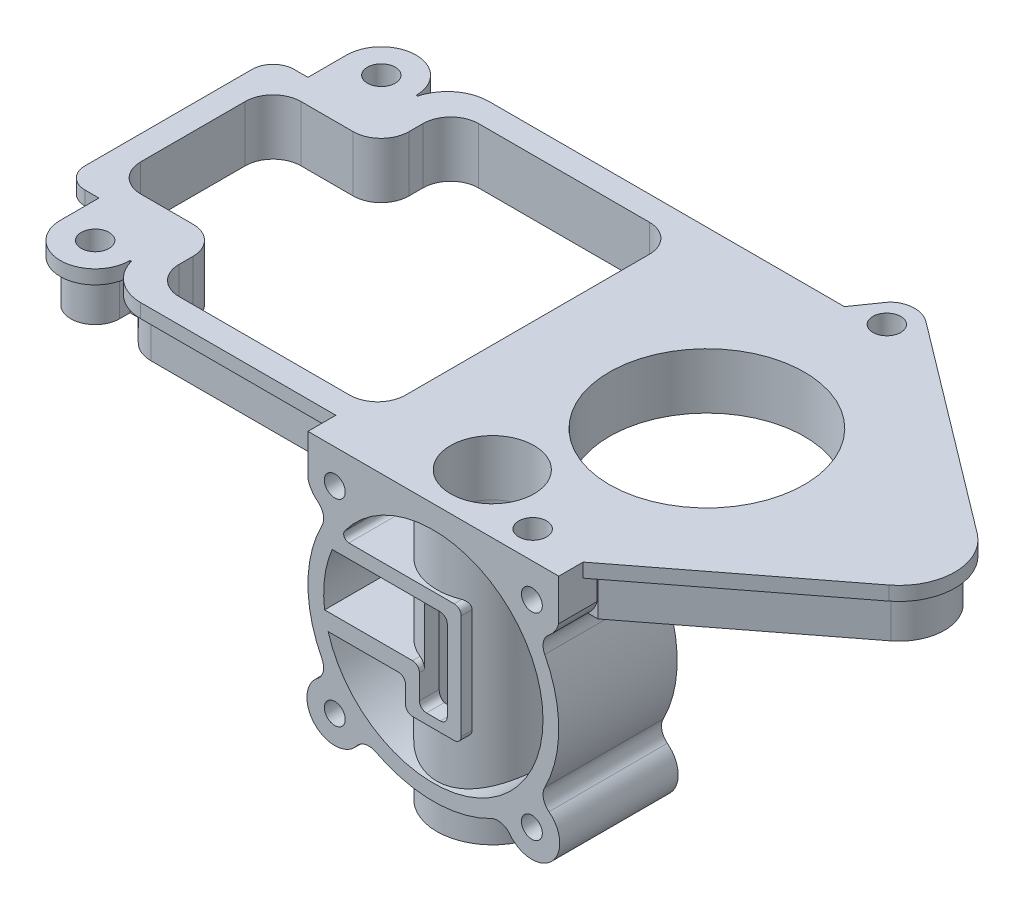
SolidWorks part; units mm, degrees
ref_plane "Płaszczyzna przednia" through (0, 0, 0) normal (0, 0, 1) x (1, 0, 0)
ref_plane "Płaszczyzna górna" through (0, 0, 0) normal (0, 1, 0) x (1, 0, 0)
ref_plane "Płaszczyzna prawa" through (0, 0, 0) normal (1, 0, 0) x (0, 0, -1)
sketch "Szkic1" plane through (0, 0, 0) normal (0, 0, 1) x (1, 0, 0)
  line L2 (-15.6121, -2) -> (-3, -2)
  line L5 (18, 19) -> (-18, 19)
  line L6 (18, 19) -> (18, 13.0853)
  line L7 (-18, 19) -> (-18, 13.0853)
  line L8 (-14.5245, 6.0642) -> (1, 6.0642)
  line L9 (4, 7.0642) -> (4, -7.9358)
  line L10 (-1, -7.5) -> (1, -7.5)
  line L12 (-15.1017, -4.4358) -> (-5, -4.4358)
  line L13 (-12.1244, 8.0642) -> (3, 8.0642)
  line L14 (-3, -8.9358) -> (3, -8.9358)
  line L15 (-2, -6.5) -> (-2, -3)
  line L16 (-4, -7.9358) -> (-4, -5.4358)
  line L17 (2, 5.0642) -> (2, -6.5)
  arc A0 (-15.1017, -4.4358) -> (-12.731, 9.2552) centre (0, 0) ccw
  arc A1 (15.9916, -8.2625) -> (15.9916, 8.2625) centre (0, 0) ccw
  arc A2 (16.5919, 10.98) -> (18, 13.0853) centre (14.1421, 14.1421) ccw
  arc A3 (-18, 13.0853) -> (-16.5919, 10.98) centre (-14.1421, 14.1421) ccw
  arc A4 (-16.5919, -10.98) -> (-10.98, -16.5919) centre (-14.1421, -14.1421) ccw
  arc A5 (10.98, -16.5919) -> (16.5919, -10.98) centre (14.1421, -14.1421) ccw
  circle A6 centre (14.1421, -14.1421) radius 1.5
  circle A7 centre (-14.1421, -14.1421) radius 1.5
  circle A8 centre (-14.1421, 14.1421) radius 1.5
  circle A9 centre (14.1421, 14.1421) radius 1.5
  arc A10 (16.5919, 10.98) -> (15.9916, 8.2625) centre (17.9238, 9.2608) ccw
  arc A13 (-15.9916, 8.2625) -> (-16.5919, 10.98) centre (-17.9238, 9.2608) ccw
  arc A14 (-16.5919, -10.98) -> (-15.9916, -8.2625) centre (-17.9238, -9.2608) ccw
  arc A15 (-8.2625, -15.9916) -> (-10.98, -16.5919) centre (-9.2608, -17.9238) ccw
  arc A16 (10.98, -16.5919) -> (8.2625, -15.9916) centre (9.2608, -17.9238) ccw
  arc A17 (15.9916, -8.2625) -> (16.5919, -10.98) centre (17.9238, -9.2608) ccw
  arc A18 (-8.2625, -15.9916) -> (8.2625, -15.9916) centre (0, 0) ccw
  arc A19 (-15.9916, 8.2625) -> (-15.9916, -8.2625) centre (0, 0) ccw
  arc A20 (-14.5245, 6.0642) -> (-15.6121, -2) centre (0, 0) ccw
  arc A21 (1, 6.0642) -> (2, 5.0642) centre (1, 5.0642) cw
  arc A22 (3, 8.0642) -> (4, 7.0642) centre (3, 7.0642) cw
  arc A23 (4, -7.9358) -> (3, -8.9358) centre (3, -7.9358) cw
  arc A24 (1, -7.5) -> (2, -6.5) centre (1, -6.5) ccw
  arc A25 (-2, -6.5) -> (-1, -7.5) centre (-1, -6.5) ccw
  arc A26 (-3, -2) -> (-2, -3) centre (-3, -3) cw
  arc A27 (-5, -4.4358) -> (-4, -5.4358) centre (-5, -5.4358) cw
  arc A28 (-4, -7.9358) -> (-3, -8.9358) centre (-3, -7.9358) ccw
  arc A29 (-12.731, 9.2552) -> (-12.1244, 8.0642) centre (-12.1244, 8.8142) ccw
  dimension "D1" = 3
  dimension "D2" = 15.7397
  dimension "D7" = 0.75
  dimension "D6" = 1
  dimension "D13" = 19
  dimension "D10" = 10.98
  dimension "D26" = 15.1017
  dimension "D27" = 15.6121
  dimension "D4" = 4
  dimension "D3" = 18
  dimension "D5" = 2.1748
  dimension "D8" = 2
  dimension "D9" = 8.2625
  dimension "D11" = 2
  dimension "D12" = 12.1244
  dimension "D14" = 7.5
  dimension "D15" = 8.9358
extrude "Dodanie-wyciągnięcie1" add sketch "Szkic1" against normal blind 17 contours A18 A16 A5 A17 A1 A10 A2 L6 L5 L7 A3 A13 A19 A14 A4 A15
extrude "Wytnij-wyciągnięcie2" cut sketch "Szkic1<4>" against normal blind 17 flip side to cut
sketch "Szkic1<4>" plane through (0, 0, 0) normal (0, 0, 1) x (1, 0, 0) same geometry as "Szkic1"
ref_plane "Płaszczyzna2" through (0, 19, 0) normal (0, 1, 0) x (1, 0, 0)
sketch "Szkic4" plane through (0, 19, 0) normal (0, 1, 0) x (1, 0, 0)
  circle A0 centre (0, 8.5) radius 6
  circle A1 centre (0, 8.5) radius 8
  dimension "D1" = 12
  dimension "D3" = 16
  dimension "D2" = 8.5
extrude "Dodanie-wyciągnięcie2" add sketch "Szkic4" against normal blind 41 contours A1
extrude "Wytnij-wyciągnięcie4" cut sketch "Szkic4<4>" against normal blind 40.7 and the other way blind 3 contours A0
sketch "Szkic4<4>" plane through (0, 19, 0) normal (0, 1, 0) x (1, 0, 0) same geometry as "Szkic4"
sketch "Szkic6" plane through (0, 0, 0) normal (0, 0, 1) x (1, 0, 0)
  line L0 (2, 5.0642) -> (2, -6.5)
  line L1 (1, -7.5) -> (-1, -7.5)
  line L2 (-2, -6.5) -> (-2, 5.0642)
  line L3 (1, 6.0642) -> (-1, 6.0642)
  arc A0 (1, -7.5) -> (2, -6.5) centre (1, -6.5) ccw construction
  arc A1 (-2, -6.5) -> (-1, -7.5) centre (-1, -6.5) ccw construction
  arc A2 (2, 5.0642) -> (1, 6.0642) centre (1, 5.0642) ccw
  arc A4 (2, -6.5) -> (1, -7.5) centre (1, -6.5) cw
  arc A5 (-2, -6.5) -> (-1, -7.5) centre (-1, -6.5) ccw
  arc A6 (-1, 6.0642) -> (-2, 5.0642) centre (-1, 5.0642) ccw
  dimension "D1" = 1
extrude "Wytnij-wyciągnięcie5" cut sketch "Szkic6" against normal blind 6
sketch "Szkic7" plane through (0, 19, 0) normal (0, 1, 0) x (1, 0, 0)
  line L0 (-18, 0) -> (18, 0)
  line L1 (18, 0) -> (18, 3.5)
  line L2 (18, 17) -> (18, 0) construction
  line L3 (-18, 0) -> (-18, 4)
  line L4 (-18, 17) -> (-18, 0) construction
  line L5 (-18, 4) -> (-46, 4)
  line L7 (-62, 14) -> (-64, 14)
  line L8 (-67, 17) -> (-67, 41)
  line L9 (-64, 44) -> (-62, 44)
  line L11 (-46, 54) -> (5, 54)
  line L12 (-52, 49.5362) -> (-51.8, 49.5362)
  line L14 (18, 3.5) -> (42.8057, 22.5981)
  line L15 (-90.7543, 29) -> (86.6637, 29) construction
  line L16 (42.7449, 35.3222) -> (18, 54)
  line L17 (-52, 8.4638) -> (-51.8, 8.4638)
  line L18 (18, 54) -> (12.6691, 58.0239)
  line L19 (-62, 14) -> (-62, 8.4638)
  line L20 (-62, 44) -> (-62, 49.5362)
  line L21 (8.9523, 58.6122) -> (9.0129, 58.6321)
  line L23 (7.4266, 57.4781) -> (5, 54)
  arc A0 (42.8057, 22.5981) -> (42.7449, 35.3222) centre (37.9253, 28.937) ccw
  arc A1 (-64, 14) -> (-67, 17) centre (-64, 17) cw
  arc A2 (-64, 44) -> (-67, 41) centre (-64, 41) ccw
  arc A5 (-46, 4) -> (-51.8, 8.4638) centre (-46, 10) cw
  arc A6 (-51.8, 49.5362) -> (-46, 54) centre (-46, 48) cw
  arc A7 (-62, 8.4638) -> (-57, 3.4638) centre (-57, 8.4638) ccw
  arc A8 (-57, 3.4638) -> (-52, 8.4638) centre (-57, 8.4638) ccw
  arc A9 (12.6691, 58.0239) -> (9.0129, 58.6321) centre (10.2592, 54.8312) ccw
  arc A10 (7.4266, 57.4781) -> (8.9523, 58.6122) centre (9.887, 55.7616) cw
  arc A11 (-62, 49.5362) -> (-57, 54.5362) centre (-57, 49.5362) cw
  arc A12 (-57, 54.5362) -> (-52, 49.5362) centre (-57, 49.5362) cw
  point P24 (51.1208, 29)
  point P27 (-67, 14)
  point P30 (-67, 44)
  point P33 (0, 0)
  point P38 (-52, 54)
  point P44 (-62, 4)
  point P62 (0, 0)
  dimension "D12" = 8
  dimension "D13" = 3
  dimension "D14" = 3
  dimension "D17" = 5
  dimension "D3" = 4
  dimension "D7" = 31.3059
  dimension "D2" = 6
  dimension "D4" = 28
  dimension "D5" = 51
  dimension "D6" = 31.0028
  dimension "D8" = 57
  dimension "D10" = 24
  dimension "D11" = 2
  dimension "D15" = 0.2
  dimension "D19" = 41
  dimension "D20" = 1.002
  dimension "D21" = 54.8312
  dimension "D22" = 55.7616
extrude "Dodanie-wyciągnięcie6" add sketch "Szkic7" against normal blind 2 contours L11 L23 A10 L21 A9 L18 L16 A0 L14 L1 L0 L3 L5 A5 L17 A8 A7 L19 L7 A1 L8 A2 L9 L20 A11 A12 L12 A6
ref_plane "Płaszczyzna4" through (0, 17, 0) normal (0, -1, 0) x (-1, 0, 0)
sketch "Szkic9" plane through (0, 17, 0) normal (0, -1, 0) x (-1, 0, 0)
  line L0 (53.5, 8.4638) -> (53.5, 9.9638)
  line L1 (50.35, 8.8478) -> (50.35, 9.9638)
  line L2 (18, 5.5) -> (46, 5.5)
  line L3 (-18.1389, 5.5) -> (46, 5.5)
  line L4 (53.5, 49.5362) -> (53.5, 48.0362)
  line L5 (60.5, 8.4638) -> (60.5, 14)
  line L6 (60.5, 8.4638) -> (60.5, 15.5)
  line L7 (-41.8906, 23.7866) -> (-17.0849, 4.6885)
  line L8 (52, 9.9638) -> (51.8, 9.9638)
  line L9 (53.5, 9.9638) -> (50.35, 9.9638)
  line L10 (-41.8906, 23.7866) -> (-18.1389, 5.5)
  line L11 (50.35, 49.1522) -> (50.35, 48.0362)
  line L12 (-41.8413, 34.125) -> (-11.7654, 56.8266)
  line L13 (-41.8413, 34.125) -> (-11.7654, 56.8266)
  line L15 (65.5, 17) -> (65.5, 41)
  line L16 (62, 15.5) -> (64, 15.5)
  line L17 (65.5, 17) -> (65.5, 41)
  line L18 (60.5, 15.5) -> (64, 15.5)
  line L27 (60.5, 42.5) -> (60.5, 49.5362)
  line L28 (64, 42.5) -> (60.5, 42.5)
  line L29 (60.5, 42.5) -> (60.5, 49.5362)
  line L30 (64, 42.5) -> (60.5, 42.5)
  line L31 (52, 48.0362) -> (51.8, 48.0362)
  line L32 (53.5, 48.0362) -> (50.35, 48.0362)
  line L43 (-5.7825, 52.5) -> (-8.6568, 56.6198)
  line L44 (46, 52.5) -> (-5.7825, 52.5)
  line L45 (-5.7825, 52.5) -> (-8.6568, 56.6198)
  line L46 (46, 52.5) -> (-5.7825, 52.5)
  arc A2 (46, 5.5) -> (50.35, 8.8478) centre (46, 10) ccw
  arc A3 (46, 5.5) -> (50.35, 8.8478) centre (46, 10) ccw
  arc A4 (-41.8413, 34.125) -> (-41.8906, 23.7866) centre (-37.9253, 28.937) ccw
  arc A5 (-41.8413, 34.125) -> (-41.8906, 23.7866) centre (-37.9253, 28.937) ccw
  arc A6 (53.5, 8.4638) -> (60.5, 8.4638) centre (57, 8.4638) ccw
  arc A7 (53.5, 8.4638) -> (60.5, 8.4638) centre (57, 8.4638) ccw
  arc A9 (-9.4803, 57.2068) -> (-11.7654, 56.8266) centre (-10.2592, 54.8312) ccw
  arc A10 (64, 15.5) -> (65.5, 17) centre (64, 17) ccw
  arc A11 (64, 15.5) -> (65.5, 17) centre (64, 17) ccw
  arc A12 (-9.4462, 57.1953) -> (-11.7654, 56.8266) centre (-10.2592, 54.8312) ccw
  arc A19 (60.5, 49.5362) -> (53.5, 49.5362) centre (57, 49.5362) ccw
  arc A20 (65.5, 41) -> (64, 42.5) centre (64, 41) ccw
  arc A21 (60.5, 49.5362) -> (53.5, 49.5362) centre (57, 49.5362) ccw
  arc A22 (65.5, 41) -> (64, 42.5) centre (64, 41) ccw
  arc A33 (-8.6568, 56.6198) -> (-9.4196, 57.1869) centre (-9.887, 55.7616) ccw
  arc A34 (50.35, 49.1522) -> (46, 52.5) centre (46, 48) ccw
  arc A35 (-8.6568, 56.6198) -> (-9.4462, 57.1953) centre (-9.887, 55.7616) ccw
  arc A36 (50.35, 49.1522) -> (46, 52.5) centre (46, 48) ccw
  point P1 (0, 0)
  dimension "D1" = 1.5
  dimension "D2" = 1.5
  dimension "D3" = 1.5
  dimension "D4" = 1.5
  dimension "D5" = 1.5
  dimension "D6" = 1.5
  dimension "D7" = 1.5
  dimension "D8" = 1.5
  dimension "D9" = 1.5
  dimension "D10" = 1.5
  dimension "D11" = 1.5
extrude "Dodanie-wyciągnięcie7" add sketch "Szkic9" along normal blind 6 contours L46 L45 A35 A12 L13 A5 L10 L3 A3 L1 L9 L0 A7 L6 L18 A11 L17 A22 L30 L29 A21 L4 L32 L11 A36
sketch "Szkic10" plane through (0, 19, 0) normal (0, 1, 0) x (1, 0, 0)
  line L0 (-59.5, 40.5) -> (-52, 40.5)
  line L1 (-44, 50.5) -> (-19.5, 50.5)
  line L2 (-63.5, 21.5) -> (-63.5, 36.5)
  line L3 (-48, 44.5) -> (-48, 46.5)
  line L4 (-48, 11.5) -> (-48, 13.5)
  line L5 (-52, 17.5) -> (-59.5, 17.5)
  line L6 (-15.5, 11.5) -> (-15.5, 46.5)
  line L7 (-19.5, 7.5) -> (-44, 7.5)
  line L8 (-62, 44) -> (-62, 49.5362) construction
  line L9 (-46, 54) -> (5, 54) construction
  arc A0 (-44, 7.5) -> (-48, 11.5) centre (-44, 11.5) cw
  arc A1 (-19.5, 7.5) -> (-15.5, 11.5) centre (-19.5, 11.5) ccw
  arc A2 (-48, 46.5) -> (-44, 50.5) centre (-44, 46.5) cw
  arc A3 (-15.5, 46.5) -> (-19.5, 50.5) centre (-19.5, 46.5) ccw
  arc A4 (-48, 13.5) -> (-52, 17.5) centre (-52, 13.5) ccw
  arc A5 (-52, 40.5) -> (-48, 44.5) centre (-52, 44.5) ccw
  arc A6 (-59.5, 40.5) -> (-63.5, 36.5) centre (-59.5, 36.5) ccw
  arc A7 (-63.5, 21.5) -> (-59.5, 17.5) centre (-59.5, 21.5) ccw
  circle A8 centre (10.2592, 29) radius 14
  circle A9 centre (10.2592, 54.8312) radius 2
  circle A10 centre (-57, 8.4638) radius 2
  circle A11 centre (-57, 49.5362) radius 2
  circle A12 centre (10.2592, 4) radius 2
  circle A13 centre (0, 8.4638) radius 6
  dimension "D1" = 4
  dimension "D2" = 14
  dimension "D3" = 46.5
  dimension "D4" = 1.5
  dimension "D5" = 3.5
  dimension "D6" = 13.5
  dimension "D7" = 36.5
extrude "Wytnij-wyciągnięcie11" cut sketch "Szkic10" against normal blind 8
